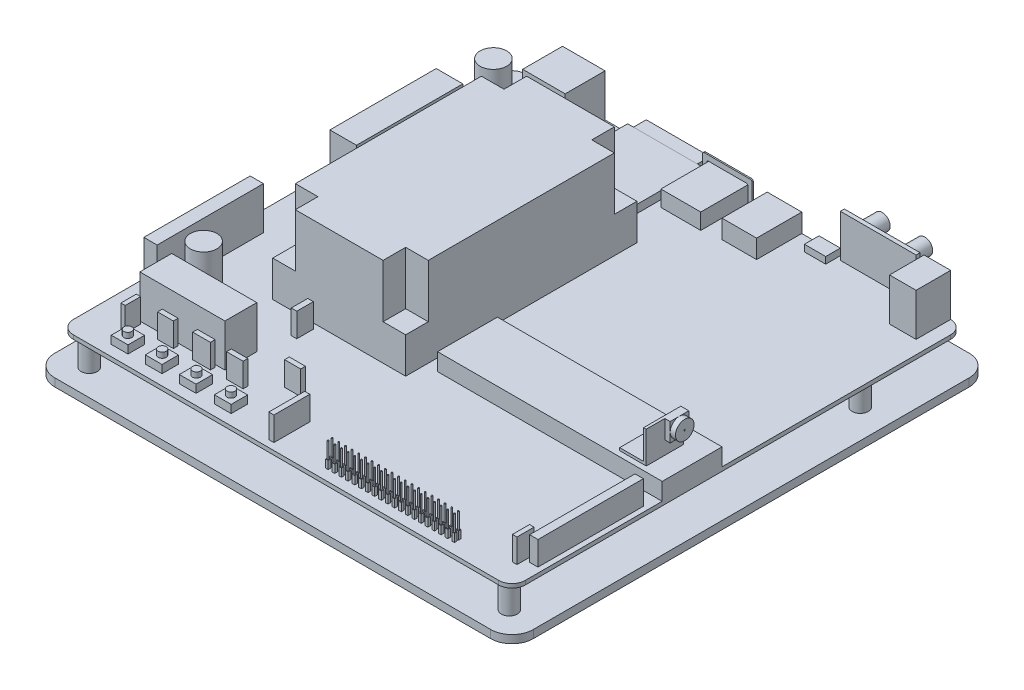
SolidWorks part; units mm, degrees
ref_plane "Plano frontal" through (0, 0, 0) normal (0, 0, 1) x (1, 0, 0)
ref_plane "Plano superior" through (0, 0, 0) normal (0, 1, 0) x (1, 0, 0)
ref_plane "Plano direito" through (0, 0, 0) normal (1, 0, 0) x (0, 0, -1)
sketch "Esboço1" plane through (0, 0, 0) normal (0, 1, 0) x (1, 0, 0)
  line L1 (82, -90) -> (-82, -90)
  line L2 (90, -82) -> (90, 82)
  line L3 (82, 90) -> (-82, 90)
  line L4 (-90, -82) -> (-90, 82)
  line L5 (90, -90) -> (-90, 90) construction
  line L6 (90, 90) -> (-90, -90) construction
  arc A0 (82, -90) -> (90, -82) centre (82, -82) ccw
  arc A1 (-82, -90) -> (-90, -82) centre (-82, -82) cw
  arc A2 (90, 82) -> (82, 90) centre (82, 82) ccw
  arc A3 (-82, 90) -> (-90, 82) centre (-82, 82) ccw
  point P0 (0, 0)
  dimension "D3" = 8
  dimension "D1" = 180
  dimension "D2" = 180
extrude "Ressalto-extrusão1" add sketch "Esboço1" along normal blind 3
sketch "Esboço2" plane through (0, 0, 0) normal (0, -1, 0) x (-1, 0, 0)
  line L0 (82, -90) -> (-82, -90) construction
  line L1 (90, 82) -> (90, -82) construction
  line L2 (0, 0) -> (-90, 0) construction
  line L3 (-90, -82) -> (-90, 82) construction
  line L4 (0, 0) -> (0, -90) construction
  circle A0 centre (79, -62) radius 3.5
  circle A1 centre (-79, -62) radius 3.5
  circle A2 centre (-79, 62) radius 3.5
  circle A3 centre (79, 62) radius 3.5
  dimension "D1" = 7
  dimension "D2" = 28
  dimension "D3" = 11
extrude "Ressalto-extrusão2" add sketch "Esboço2" along normal blind 5
sketch "Esboço3" plane through (0, 3, 0) normal (0, 1, 0) x (1, 0, 0)
  line L0 (90, -82) -> (90, 82) construction
  line L1 (-82, -90) -> (82, -90) construction
  line L2 (-90, 82) -> (-90, -82) construction
  line L3 (82, 90) -> (-82, 90) construction
  circle A0 centre (-79, -80) radius 3
  circle A1 centre (-79, 75) radius 3
  circle A2 centre (79, 52) radius 3
  circle A3 centre (79, -80) radius 3
  dimension "D1" = 6
  dimension "D3" = 11
  dimension "D5" = 10
  dimension "D6" = 38
  dimension "D2" = 10
  dimension "D4" = 11
  dimension "D7" = 15
extrude "Ressalto-extrusão3" add sketch "Esboço3" along normal blind 11
sketch "Esboço4" plane through (0, 14, 0) normal (0, 1, 0) x (1, 0, 0)
  line L1 (-80, 85) -> (80, 85)
  line L2 (-85, 80) -> (-85, -80)
  line L3 (-80, -85) -> (80, -85)
  line L4 (85, 80) -> (85, -80)
  line L5 (-85, 85) -> (85, -85) construction
  line L6 (-85, -85) -> (85, 85) construction
  arc A1 (80, -85) -> (85, -80) centre (80, -80) ccw
  arc A2 (-85, -80) -> (-80, -85) centre (-80, -80) ccw
  arc A3 (80, 85) -> (85, 80) centre (80, 80) cw
  arc A4 (-80, 85) -> (-85, 80) centre (-80, 80) ccw
  point P0 (0, 0)
  dimension "D3" = 5
  dimension "D1" = 170
  dimension "D2" = 170
extrude "Ressalto-extrusão4" add sketch "Esboço4" along normal blind 1.5
sketch "Esboço5" plane through (0, 15.5, 0) normal (0, 1, 0) x (1, 0, 0)
  line L0 (-80, -85) -> (80, -85) construction
  line L1 (-54, 51) -> (-4, 51)
  line L2 (-54, 51) -> (-54, -36)
  line L3 (-54, -36) -> (-4, -36)
  line L4 (-4, 51) -> (-4, -36)
  line L5 (-54, 51) -> (-4, -36) construction
  line L6 (-54, -36) -> (-4, 51) construction
  line L7 (-85, 80) -> (-85, -80) construction
  point P0 (-29, 7.5)
  dimension "D1" = 50
  dimension "D2" = 87
  dimension "D3" = 49
  dimension "D4" = 31
extrude "Ressalto-extrusão5" add sketch "Esboço5" along normal blind 33.5
sketch "Esboço6" plane through (0, 49, 0) normal (0, 1, 0) x (1, 0, 0)
  line L0 (-54, 7.5) -> (-4, 7.5) construction
  line L1 (-54, -36) -> (-45.5, -36)
  line L2 (-54, -36) -> (-54, -27.5)
  line L3 (-54, -27.5) -> (-45.5, -27.5)
  line L4 (-45.5, -36) -> (-45.5, -27.5)
  line L5 (-54, 51) -> (-54, -36) construction
  line L6 (-4, -36) -> (-4, 51) construction
  line L7 (-29, 51) -> (-29, -36) construction
  line L8 (-4, 51) -> (-54, 51) construction
  line L9 (-54, -36) -> (-4, -36) construction
  line L10 (-12.5, -36) -> (-12.5, -27.5)
  line L11 (-4, -36) -> (-12.5, -36)
  line L12 (-4, -36) -> (-4, -27.5)
  line L13 (-4, -27.5) -> (-12.5, -27.5)
  line L14 (-4, 42.5) -> (-12.5, 42.5)
  line L15 (-4, 51) -> (-4, 42.5)
  line L16 (-4, 51) -> (-12.5, 51)
  line L17 (-12.5, 51) -> (-12.5, 42.5)
  line L18 (-45.5, 51) -> (-45.5, 42.5)
  line L19 (-54, 42.5) -> (-45.5, 42.5)
  line L20 (-54, 51) -> (-54, 42.5)
  line L21 (-54, 51) -> (-45.5, 51)
  dimension "D1" = 8.5
  dimension "D2" = 8.5
extrude "Corte-extrusão1" cut sketch "Esboço6" against normal blind 20
sketch "Esboço7" plane through (0, 15.5, 0) normal (0, 1, 0) x (1, 0, 0)
  line L0 (-30.95, -74.8) -> (-24.65, -74.8)
  line L1 (-69.75, -74.8) -> (-63.45, -74.8)
  line L2 (-69.75, -74.8) -> (-69.75, -81)
  line L3 (-69.75, -81) -> (-63.45, -81)
  line L4 (-63.45, -74.8) -> (-63.45, -81)
  line L5 (-69.75, -74.8) -> (-63.45, -81) construction
  line L6 (-69.75, -81) -> (-63.45, -74.8) construction
  line L7 (-80, -85) -> (80, -85) construction
  line L8 (-85, 80) -> (-85, -80) construction
  line L9 (-56.95, -74.8) -> (-50.65, -74.8)
  line L10 (-56.95, -74.8) -> (-56.95, -81)
  line L11 (-56.95, -81) -> (-50.65, -81)
  line L12 (-50.65, -74.8) -> (-50.65, -81)
  line L13 (-56.95, -74.8) -> (-50.65, -81) construction
  line L14 (-56.95, -81) -> (-50.65, -74.8) construction
  line L15 (-44.15, -74.8) -> (-37.85, -74.8)
  line L16 (-44.15, -74.8) -> (-44.15, -81)
  line L17 (-44.15, -81) -> (-37.85, -81)
  line L18 (-37.85, -74.8) -> (-37.85, -81)
  line L19 (-44.15, -74.8) -> (-37.85, -81) construction
  line L20 (-44.15, -81) -> (-37.85, -74.8) construction
  line L21 (-30.95, -74.8) -> (-30.95, -81)
  line L22 (-30.95, -81) -> (-24.65, -81)
  line L23 (-24.65, -74.8) -> (-24.65, -81)
  line L24 (-30.95, -74.8) -> (-24.65, -81) construction
  line L25 (-30.95, -81) -> (-24.65, -74.8) construction
  point P0 (-66.6, -77.9)
  point P10 (-27.8, -77.9)
  point P11 (-53.8, -77.9)
  point P16 (-41, -77.9)
  dimension "D1" = 6.2
  dimension "D2" = 6.3
  dimension "D3" = 4
  dimension "D4" = 15.25
  dimension "D5" = 3
  dimension "D6" = 6.5
  dimension "D8" = 6.9
  dimension "D7" = 2
extrude "Ressalto-extrusão6" add sketch "Esboço7" along normal blind 3
sketch "Esboço8" plane through (0, 18.5, 0) normal (0, 1, 0) x (1, 0, 0)
  line L0 (-63.45, -81) -> (-63.45, -74.8) construction
  line L2 (-69.75, -81) -> (-63.45, -81) construction
  line L3 (-24.65, -81) -> (-24.65, -74.8) construction
  line L4 (-24.65, -74.8) -> (-30.95, -74.8) construction
  circle A0 centre (-66.6, -77.9) radius 1.5
  circle A1 centre (-53.7, -77.9) radius 1.5
  circle A2 centre (-40.8, -77.9) radius 1.5
  circle A3 centre (-27.75, -77.95) radius 1.5
  point P6 (-66.6, -81)
  dimension "D1" = 3.15
  dimension "D2" = 3.1
  dimension "D3" = 3
  dimension "D5" = 3
  dimension "D6" = 3.1
  dimension "D7" = 3.15
  dimension "D8" = 12.9
  dimension "D4" = 3
extrude "Ressalto-extrusão7" add sketch "Esboço8" along normal blind 2
sketch "Esboço9" plane through (0, 15.5, 0) normal (0, 1, 0) x (1, 0, 0)
  line L0 (-80, -85) -> (80, -85) construction
  line L1 (10.85, -80) -> (11.85, -80)
  line L2 (10.85, -80) -> (10.85, -81)
  line L3 (10.85, -81) -> (11.85, -81)
  line L4 (11.85, -80) -> (11.85, -81)
  line L5 (10.85, -80) -> (11.85, -81) construction
  line L6 (10.85, -81) -> (11.85, -80) construction
  line L7 (-24.65, -81) -> (-24.65, -74.8) construction
  point P0 (11.35, -80.5)
  dimension "D1" = 1
  dimension "D2" = 4
  dimension "D3" = 35.5
extrude "Ressalto-extrusão8" add sketch "Esboço9" along normal blind 3
sketch "Esboço10" plane through (0, 18.5, 0) normal (0, 1, 0) x (1, 0, 0)
  line L1 (11.35, -80) -> (11.35, -80.5) construction
  line L2 (11.85, -80) -> (10.85, -80) construction
  line L3 (11.35, -80.5) -> (11.85, -80.5) construction
  line L4 (11.85, -81) -> (11.85, -80) construction
  circle A0 centre (11.35, -80.5) radius 0.25
  dimension "D1" = 0.5
extrude "Ressalto-extrusão9" add sketch "Esboço10" along normal blind 6
pattern_linear "Padrão linear1" count 20 spacing 2.5 along (1, 0, 0) count 2 spacing 1.5 along (0, 0, -1) of "Ressalto-extrusão8", "Ressalto-extrusão9"
sketch "Esboço11" plane through (0, 15.5, 0) normal (0, 1, 0) x (1, 0, 0)
  line L0 (80, 85) -> (-80, 85) construction
  line L1 (-71.9966, -56) -> (-39.9966, -56)
  line L2 (-71.9966, -56) -> (-71.9966, -68)
  line L3 (-71.9966, -68) -> (-39.9966, -68)
  line L4 (-39.9966, -56) -> (-39.9966, -68)
  line L5 (-82.5, -56) -> (-77.5, -56)
  line L6 (-82.5, -56) -> (-82.5, -16)
  line L7 (-82.5, -16) -> (-77.5, -16)
  line L8 (-77.5, -56) -> (-77.5, -16)
  line L9 (-82.5, 54) -> (-72.5, 54)
  line L10 (-82.5, 54) -> (-82.5, 14)
  line L11 (-82.5, 14) -> (-72.5, 14)
  line L12 (-72.5, 54) -> (-72.5, 14)
  line L13 (-66, 85) -> (-50, 85)
  line L14 (-66, 85) -> (-66, 70)
  line L15 (-66, 70) -> (-50, 70)
  line L16 (-50, 85) -> (-50, 70)
  line L17 (-85, 80) -> (-85, -80) construction
  line L18 (-80, -85) -> (80, -85) construction
  line L19 (80, 85) -> (70, 85)
  line L20 (80, 85) -> (80, 72)
  line L21 (80, 72) -> (70, 72)
  line L22 (70, 85) -> (70, 72)
  line L23 (68.5, 85) -> (40, 85)
  line L24 (68.5, 85) -> (68.5, 83.5)
  line L25 (68.5, 83.5) -> (40, 83.5)
  line L26 (40, 85) -> (40, 83.5)
  circle A0 centre (-70, -46) radius 5
  circle A1 centre (-75, 68) radius 5
  dimension "D1" = 10
  dimension "D2" = 10
  dimension "D12" = 17
  dimension "D26" = 10
  dimension "D3" = 15
  dimension "D4" = 16
  dimension "D5" = 19
  dimension "D6" = 13
  dimension "D7" = 10
  dimension "D8" = 28.5
  dimension "D9" = 1.5
  dimension "D10" = 1.5
  dimension "D11" = 10
  dimension "D13" = 10
  dimension "D14" = 40
  dimension "D15" = 2.5
  dimension "D16" = 2.5
  dimension "D17" = 5
  dimension "D18" = 29
  dimension "D19" = 30
  dimension "D20" = 40
  dimension "D21" = 7.5
  dimension "D22" = 12
  dimension "D23" = 32
  dimension "D24" = 13.0034
  dimension "D25" = 17
extrude "Ressalto-extrusão10" add sketch "Esboço11" along normal blind 16
sketch "Esboço12" plane through (0, 0, -85) normal (0, 0, -1) x (-1, 0, 0)
  line L0 (-68.5, 31.5) -> (-40, 31.5) construction
  line L1 (-62.25, 26.5) -> (-68.5, 26.5) construction
  line L2 (-68.5, 31.5) -> (-68.5, 15.5) construction
  line L3 (-46.25, 26.5) -> (-40, 26.5) construction
  line L4 (-40, 31.5) -> (-40, 15.5) construction
  circle A0 centre (-62.25, 26.5) radius 3
  circle A1 centre (-46.25, 26.5) radius 3
  dimension "D1" = 6
  dimension "D2" = 6
  dimension "D3" = 5
  dimension "D4" = 16
extrude "Ressalto-extrusão11" add sketch "Esboço12" along normal blind 8
sketch "Esboço13" plane through (0, 15.5, 0) normal (0, 1, 0) x (1, 0, 0)
  line L0 (-69.75, -74.8) -> (-69.75, -81) construction
  line L1 (-70.7943, -68.907) -> (-72.4259, -68.907)
  line L2 (-70.7943, -68.907) -> (-70.7943, -74.6918)
  line L3 (-70.7943, -74.6918) -> (-72.4259, -74.6918)
  line L4 (-72.4259, -68.907) -> (-72.4259, -74.6918)
  line L5 (-62.6363, -68.907) -> (-56.7033, -68.907)
  line L6 (-62.6363, -68.907) -> (-62.6363, -70.6869)
  line L7 (-62.6363, -70.6869) -> (-56.7033, -70.6869)
  line L8 (-56.7033, -68.907) -> (-56.7033, -70.6869)
  line L9 (-49.4353, -68.907) -> (-42.7606, -68.907)
  line L10 (-49.4353, -68.907) -> (-49.4353, -70.6869)
  line L11 (-49.4353, -70.6869) -> (-42.7606, -70.6869)
  line L12 (-42.7606, -68.907) -> (-42.7606, -70.6869)
  line L13 (-36.6792, -68.907) -> (-30.4495, -68.907)
  line L14 (-36.6792, -68.907) -> (-36.6792, -70.6869)
  line L15 (-36.6792, -70.6869) -> (-30.4495, -70.6869)
  line L16 (-30.4495, -68.907) -> (-30.4495, -70.6869)
  line L17 (-9.0905, -68.907) -> (-7.1623, -68.907)
  line L18 (-9.0905, -68.907) -> (-9.0905, -82.4047)
  line L19 (-9.0905, -82.4047) -> (-7.1623, -82.4047)
  line L20 (-7.1623, -68.907) -> (-7.1623, -82.4047)
  line L21 (-23.1815, -60.6008) -> (-17.1002, -60.6008)
  line L22 (-23.1815, -60.6008) -> (-23.1815, -62.3807)
  line L23 (-23.1815, -62.3807) -> (-17.1002, -62.3807)
  line L24 (-17.1002, -60.6008) -> (-17.1002, -62.3807)
  line L25 (-38.7558, -38.0552) -> (-36.6792, -38.0552)
  line L26 (-38.7558, -38.0552) -> (-38.7558, -44.2849)
  line L27 (-38.7558, -44.2849) -> (-36.6792, -44.2849)
  line L28 (-36.6792, -38.0552) -> (-36.6792, -44.2849)
  line L29 (83.0751, -73.3111) -> (79.9494, -73.3111)
  line L30 (83.0751, -73.3111) -> (83.0751, -33.6552)
  line L31 (83.0751, -33.6552) -> (79.9494, -33.6552)
  line L32 (79.9494, -73.3111) -> (79.9494, -33.6552)
  line L33 (78.3022, -70.0067) -> (76.6024, -70.0067)
  line L34 (78.3022, -70.0067) -> (78.3022, -76.444)
  line L35 (78.3022, -76.444) -> (76.6024, -76.444)
  line L36 (76.6024, -70.0067) -> (76.6024, -76.444)
  line L37 (-63.45, -74.8) -> (-69.75, -74.8) construction
  dimension "D1" = 7.1137
  dimension "D2" = 13.0467
  dimension "D3" = 20.3147
  dimension "D4" = 26.9894
  dimension "D5" = 30.9942
  dimension "D6" = 33.0708
  dimension "D7" = 39.3005
  dimension "D8" = 46.5685
  dimension "D9" = 52.6498
  dimension "D10" = 60.6595
  dimension "D11" = 62.5877
  dimension "D12" = 146.3524
  dimension "D13" = 148.0522
  dimension "D14" = 149.6994
  dimension "D15" = 152.8251
  dimension "D16" = 1.0443
  dimension "D17" = 2.6759
  dimension "D18" = 0.1082
  dimension "D19" = 1.4889
  dimension "D20" = 4.1131
  dimension "D21" = 4.7933
  dimension "D22" = 5.893
  dimension "D23" = 12.4193
  dimension "D24" = 30.5151
  dimension "D27" = 41.1448
  dimension "D28" = 1.644
  dimension "D29" = 7.6047
extrude "Ressalto-extrusão12" add sketch "Esboço13" along normal blind 9
sketch "Esboço14" plane through (0, 15.5, 0) normal (0, 1, 0) x (1, 0, 0)
  line L0 (85, -80) -> (85, 80) construction
  line L1 (85, -28.5) -> (0.5, -28.5)
  line L2 (85, -28.5) -> (85, -6)
  line L3 (85, -6) -> (0.5, -6)
  line L4 (0.5, -28.5) -> (0.5, -6)
  line L5 (-80, -85) -> (80, -85) construction
  dimension "D1" = 56.5
  dimension "D2" = 84.5
  dimension "D3" = 22.5
extrude "Ressalto-extrusão13" add sketch "Esboço14" along normal blind 6.5
sketch "Esboço15" plane through (0, 22, 0) normal (0, 1, 0) x (1, 0, 0)
  line L0 (85, -28.5) -> (85, -6) construction
  line L1 (77, -12.5) -> (76, -12.5)
  line L2 (77, -12.5) -> (77, -26.5)
  line L3 (77, -26.5) -> (76, -26.5)
  line L4 (76, -12.5) -> (76, -26.5)
  line L5 (0.5, -28.5) -> (85, -28.5) construction
  dimension "D1" = 14
  dimension "D2" = 1
  dimension "D3" = 8
  dimension "D4" = 2
extrude "Ressalto-extrusão14" add sketch "Esboço15" along normal blind 12
sketch "Esboço16" plane through (76, 0, 0) normal (-1, 0, 0) x (0, 0, 1)
  line L0 (26.5, 34) -> (26.5, 22) construction
  line L1 (12.5, 22) -> (26.5, 22)
  line L2 (12.5, 22) -> (12.5, 23)
  line L3 (12.5, 23) -> (26.5, 23)
  line L4 (26.5, 22) -> (26.5, 23)
  dimension "D1" = 1
extrude "Ressalto-extrusão15" add sketch "Esboço16" along normal blind 9
sketch "Esboço17" plane through (77, 0, 0) normal (1, 0, 0) x (0, 0, -1)
  line L1 (-12.5, 34) -> (-19.5, 34)
  line L2 (-12.5, 34) -> (-12.5, 27)
  line L3 (-12.5, 27) -> (-19.5, 27)
  line L4 (-19.5, 34) -> (-19.5, 27)
  dimension "D1" = 7
  dimension "D2" = 7
extrude "Ressalto-extrusão16" add sketch "Esboço17" along normal blind 2
sketch "Esboço18" plane through (79, 0, 0) normal (1, 0, 0) x (0, 0, -1)
  line L0 (-16, 34) -> (-16, 30.5) construction
  line L1 (-12.5, 34) -> (-19.5, 34) construction
  line L2 (-16, 30.5) -> (-12.5, 30.5) construction
  line L3 (-12.5, 27) -> (-12.5, 34) construction
  circle A0 centre (-16, 30.5) radius 3.5
  dimension "D1" = 7
extrude "Ressalto-extrusão17" add sketch "Esboço18" along normal blind 2
sketch "Esboço19" plane through (81, 0, 0) normal (1, 0, 0) x (0, 0, -1)
  circle A0 centre (-16, 30.5) radius 0.35
  circle A1 centre (-16, 30.5) radius 0.25
  dimension "D1" = 0.5
  dimension "D2" = 0.1
extrude "Corte-extrusão2" cut sketch "Esboço19" against normal blind 0.2
sketch "Esboço20" plane through (0, 15.5, 0) normal (0, 1, 0) x (1, 0, 0)
  line L0 (40, 85) -> (-50, 85) construction
  line L1 (-41.5, 85) -> (-13.5, 85)
  line L2 (-41.5, 85) -> (-41.5, 56)
  line L3 (-41.5, 56) -> (-13.5, 56)
  line L4 (-13.5, 85) -> (-13.5, 56)
  line L5 (-50, 70) -> (-50, 85) construction
  line L6 (-39.5, 85) -> (-15.5, 85)
  line L7 (-39.5, 85) -> (-39.5, 90)
  line L8 (-39.5, 90) -> (-15.5, 90)
  line L9 (-15.5, 85) -> (-15.5, 90)
  point P12 (-27.5, 90)
  point P13 (-27.5, 85)
  dimension "D1" = 8.5
  dimension "D2" = 28
  dimension "D3" = 29
  dimension "D4" = 5
  dimension "D5" = 24
extrude "Ressalto-extrusão18" add sketch "Esboço20" along normal blind 3 contours L1 L9 L8 L7 | L4 L1 L2 L3 region at (-27.5, 15.5, -70.5) region at (-27.5, 15.5, -87.5)
sketch "Esboço21" plane through (0, 0, -90) normal (0, 0, -1) x (-1, 0, 0)
  line L0 (15.5, 18.5) -> (15.5, 15.5) construction
  line L1 (39.5, 15.5) -> (15.5, 15.5)
  line L2 (39.5, 15.5) -> (39.5, 15.7)
  line L3 (39.5, 15.7) -> (15.5, 15.7)
  line L4 (15.5, 15.5) -> (15.5, 15.7)
  line L5 (39.5, 17) -> (15.5, 17) construction
  line L6 (39.5, 18.5) -> (39.5, 15.5) construction
  line L7 (15.5, 18.5) -> (15.5, 18.3)
  line L8 (39.5, 18.3) -> (15.5, 18.3)
  line L9 (39.5, 18.5) -> (39.5, 18.3)
  line L10 (39.5, 18.5) -> (15.5, 18.5)
  dimension "D1" = 0.2
extrude "Corte-extrusão3" cut sketch "Esboço21" against normal blind 5
sketch "Esboço22" plane through (0, 15.5, 0) normal (0, 1, 0) x (1, 0, 0)
  line L0 (40, 85) -> (-13.5, 85) construction
  line L1 (-11, 85) -> (4, 85)
  line L2 (-11, 85) -> (-11, 67)
  line L3 (-11, 67) -> (4, 67)
  line L4 (4, 85) -> (4, 67)
  line L5 (-13.5, 85) -> (-13.5, 56) construction
  dimension "D1" = 15
  dimension "D2" = 18
  dimension "D3" = 2.5
extrude "Ressalto-extrusão19" add sketch "Esboço22" along normal blind 6
sketch "Esboço23" plane through (0, 15.5, 0) normal (0, 1, 0) x (1, 0, 0)
  line L0 (40, 85) -> (4, 85) construction
  line L1 (11, 85) -> (24, 85)
  line L2 (11, 85) -> (11, 68)
  line L3 (11, 68) -> (24, 68)
  line L4 (24, 85) -> (24, 68)
  line L5 (4, 67) -> (4, 85) construction
  dimension "D1" = 13
  dimension "D2" = 17
  dimension "D3" = 7
extrude "Ressalto-extrusão20" add sketch "Esboço23" along normal blind 7
sketch "Esboço24" plane through (0, 15.5, 0) normal (0, 1, 0) x (1, 0, 0)
  line L0 (40, 85) -> (24, 85) construction
  line L1 (30.5, 85) -> (38.5, 85)
  line L2 (30.5, 85) -> (30.5, 79.5)
  line L3 (30.5, 79.5) -> (38.5, 79.5)
  line L4 (38.5, 85) -> (38.5, 79.5)
  line L5 (24, 68) -> (24, 85) construction
  dimension "D1" = 8
  dimension "D2" = 5.5
  dimension "D3" = 6.5
extrude "Ressalto-extrusão21" add sketch "Esboço24" along normal blind 2.5
sketch "Esboço25" plane through (0, 0, -85) normal (0, 0, -1) x (-1, 0, 0)
  line L0 (-3.5, 20) -> (10.5, 20)
  line L1 (10.5, 20) -> (10.5, 17)
  line L2 (10.5, 17) -> (9, 15.5)
  line L3 (9, 15.5) -> (-2, 15.5)
  line L4 (-2, 15.5) -> (-3.5, 17)
  line L5 (-3.5, 17) -> (-3.5, 20)
  line L6 (10.5, 20) -> (11, 20) construction
  line L7 (11, 21.5) -> (11, 15.5) construction
  line L8 (-3.5, 20) -> (-4, 20) construction
  line L9 (-4, 21.5) -> (-4, 15.5) construction
  line L10 (3.5, 20) -> (3.5, 21.5) construction
  line L11 (-4, 21.5) -> (11, 21.5) construction
  line L12 (3.5, 15.5) -> (3.5, 14) construction
  line L13 (-80, 14) -> (80, 14) construction
  line L14 (-1.5, 17.5) -> (-3.5, 17.5) construction
  line L15 (-1.5, 18) -> (8.5, 18)
  line L16 (-1.5, 18) -> (-1.5, 17.5)
  line L17 (-1.5, 17.5) -> (8.5, 17.5)
  line L18 (8.5, 18) -> (8.5, 17.5)
  line L19 (8.5, 17.5) -> (10.5, 17.5) construction
  point P6 (10.75, 20)
  point P28 (3.5, 15.5)
  point P29 (3.5, 20)
  dimension "D1" = 14
  dimension "D2" = 3
  dimension "D3" = 4.5
  dimension "D4" = 10
  dimension "D5" = 0.5
  dimension "D6" = 0.5
extrude "Corte-extrusão4" cut sketch "Esboço25" against normal blind 8.5
sketch "Esboço26" plane through (0, 0, -85) normal (0, 0, -1) x (-1, 0, 0)
  line L0 (-4.2, 15.5) -> (-4.2, 21.5)
  line L1 (-85, 15.5) -> (-0.5, 15.5) construction
  line L2 (-3.7, 22) -> (10.7, 22)
  line L3 (11.2, 21.5) -> (11.2, 15.5)
  line L4 (11, 15.5) -> (13.5, 15.5) construction
  line L5 (11.2, 15.5) -> (12.75, 15.5)
  line L6 (4, 15.5) -> (54, 15.5) construction
  line L7 (12.75, 15.5) -> (12.75, 23.5)
  line L8 (12.25, 24) -> (-5.25, 24)
  line L9 (-5.75, 23.5) -> (-5.75, 15.5)
  line L10 (-11, 15.5) -> (-4, 15.5) construction
  line L11 (-5.75, 15.5) -> (-4.2, 15.5)
  line L12 (-4, 21.5) -> (-4, 15.5) construction
  line L13 (11, 21.5) -> (11, 15.5) construction
  line L14 (-4, 21.5) -> (11, 21.5) construction
  arc A0 (10.7, 22) -> (11.2, 21.5) centre (10.7, 21.5) cw
  arc A1 (-4.2, 21.5) -> (-3.7, 22) centre (-3.7, 21.5) cw
  arc A2 (12.75, 23.5) -> (12.25, 24) centre (12.25, 23.5) ccw
  arc A3 (-5.25, 24) -> (-5.75, 23.5) centre (-5.25, 23.5) ccw
  point P28 (12.75, 24)
  point P31 (-5.75, 24)
  dimension "D6" = 0.5
  dimension "D1" = 8.5
  dimension "D2" = 18.5
  dimension "D3" = 0.2
  dimension "D4" = 0.2
  dimension "D5" = 0.5
extrude "Ressalto-extrusão22" add sketch "Esboço26" against normal blind 0.5
sketch "Esboço27" plane through (0, 0, -85) normal (0, 0, -1) x (-1, 0, 0)
  line L0 (-24, 22.5) -> (-24, 15.5) construction
  line L1 (-23.8, 22.3) -> (-11.2, 22.3)
  line L2 (-23.8, 22.3) -> (-23.8, 15.7)
  line L3 (-23.8, 15.7) -> (-11.2, 15.7)
  line L4 (-11.2, 22.3) -> (-11.2, 15.7)
  line L5 (-11, 22.5) -> (-11, 15.5) construction
  line L6 (-24, 22.5) -> (-11, 22.5) construction
  line L7 (-85, 15.5) -> (-0.5, 15.5) construction
  line L8 (-22.8, 21.3) -> (-12.2, 21.3)
  line L9 (-12.2, 21.3) -> (-12.2, 19.8)
  line L10 (-12.2, 21.3) -> (-12.2, 16.7) construction
  line L11 (-22.8, 21.3) -> (-22.8, 19.8)
  line L12 (-22.8, 19.8) -> (-12.2, 19.8)
  line L13 (-22.8, 21.3) -> (-22.8, 16.7) construction
  line L14 (-22.8, 16.7) -> (-12.2, 16.7) construction
  dimension "D1" = 0.2
  dimension "D2" = 0.2
  dimension "D3" = 0.2
  dimension "D4" = 0.2
  dimension "D6" = 1.5
  dimension "D5" = 1
extrude "Corte-extrusão5" cut sketch "Esboço27" against normal blind 10
sketch "Esboço28" plane through (0, 0, -85) normal (0, 0, -1) x (-1, 0, 0)
  line L0 (-40, 15.5) -> (-38.5, 15.5) construction
  line L1 (-37.3, 17.8) -> (-31.7, 17.8)
  line L2 (-38.3, 16.8) -> (-38.3, 16.7)
  line L3 (-37.3, 15.7) -> (-31.7, 15.7)
  line L4 (-30.7, 16.8) -> (-30.7, 16.7)
  line L5 (-38.5, 18) -> (-30.5, 18) construction
  line L6 (-38.5, 18) -> (-38.5, 15.5) construction
  line L7 (-30.5, 18) -> (-30.5, 15.5) construction
  arc A0 (-31.7, 15.7) -> (-30.7, 16.7) centre (-31.7, 16.7) ccw
  arc A1 (-31.7, 17.8) -> (-30.7, 16.8) centre (-31.7, 16.8) cw
  arc A2 (-38.3, 16.7) -> (-37.3, 15.7) centre (-37.3, 16.7) ccw
  arc A3 (-37.3, 17.8) -> (-38.3, 16.8) centre (-37.3, 16.8) ccw
  point P4 (0, 0)
  dimension "D5" = 1
  dimension "D1" = 0.2
  dimension "D2" = 0.2
  dimension "D3" = 0.2
  dimension "D4" = 0.2
extrude "Corte-extrusão6" cut sketch "Esboço28" against normal blind 4
